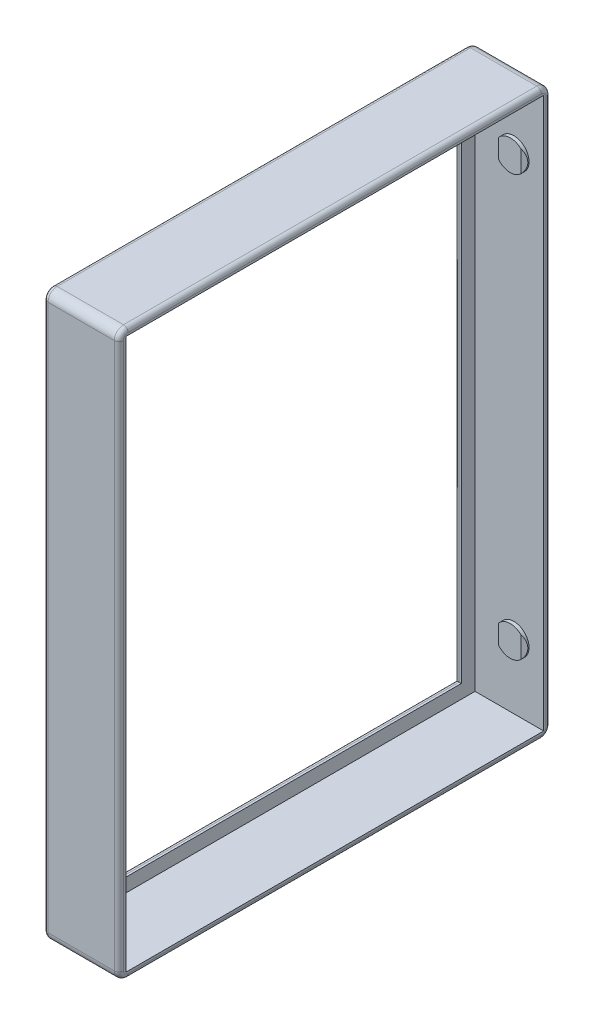
SolidWorks part; units mm, degrees
ref_plane "Front Plane" through (0, 0, 0) normal (0, 0, 1) x (1, 0, 0)
ref_plane "Top Plane" through (0, 0, 0) normal (0, 1, 0) x (1, 0, 0)
ref_plane "Right Plane" through (0, 0, 0) normal (1, 0, 0) x (0, 0, -1)
sketch "Sketch1" plane through (3.3486, 0, 0) normal (-1, 0, 0) x (0, 0, 1)
  line L0 (-28.4017, -129.0389) -> (56.9983, -129.0389)
  line L1 (56.9983, -129.0389) -> (56.9983, -14.6389)
  line L2 (56.9983, -14.6389) -> (-28.4017, -14.6389)
  line L3 (-28.4017, -14.6389) -> (-28.4017, -129.0389)
  line L4 (61.4983, -133.5389) -> (61.4983, -10.1389)
  line L5 (61.4983, -10.1389) -> (-32.9017, -10.1389)
  line L6 (-32.9017, -10.1389) -> (-32.9017, -133.5389)
  line L7 (-32.9017, -133.5389) -> (61.4983, -133.5389)
  line L8 (59.9983, -11.6389) -> (-31.4017, -11.6389)
  line L10 (59.9983, -11.6389) -> (-31.4017, -11.6389)
  line L1256 (-31.4017, -11.6389) -> (-31.4017, -132.0389)
  line L1258 (-31.4017, -11.6389) -> (-31.4017, -132.0389)
  line L1268 (-31.4017, -132.0389) -> (59.9983, -132.0389)
  line L1269 (-31.4017, -132.0389) -> (59.9983, -132.0389)
  line L1270 (59.9983, -132.0389) -> (59.9983, -11.6389)
  line L1271 (59.9983, -132.0389) -> (59.9983, -11.6389)
  dimension "D1" = 0.2
extrude "Boss-Extrude1" add sketch "Sketch1" along normal blind 1.5 contours L6 L7 L4 L5 L1271 L1269 L1258 L10 | L1269 L1271 L10 L1258 L3 L2 L1 L0 region at (3.3486, -133.3835, 14.2983) region at (3.3486, -71.8389, 58.4867)
extrude "Boss-Extrude2" add sketch "Sketch1<3>" against normal blind 15 contours L6 L7 L4 L5 L1271 L1269 L1258 L10 region at (3.3486, -133.3835, 14.2983)
sketch "Sketch1<3>" plane through (3.3486, 0, 0) normal (-1, 0, 0) x (0, 0, 1) same geometry as "Sketch1"
fillet "Fillet1" radius 2 4 edges at (10.0986, -10.1389, -32.9017) (10.0986, -133.5389, -32.9017) (10.0986, -10.1389, 61.4983) (10.0986, -133.5389, 61.4983)
fillet "Fillet2" radius 1 12 edges at (1.8486, -129.0389, 14.2983) (1.8486, -71.8389, 56.9983) (1.8486, -14.6389, 14.2983) (1.8486, -71.8389, -28.4017) (1.8486, -10.7247, 60.9125) (1.8486, -71.8389, 61.4983) (1.8486, -132.9531, 60.9125) (1.8486, -133.5389, 14.2983) (1.8486, -132.9531, -32.3159) (1.8486, -71.8389, -32.9017) (1.8486, -10.7247, -32.3159) (1.8486, -10.1389, 14.2983)
fillet "Fillet5" radius 1 8 edges at (18.3486, -10.7247, -32.3159) (18.3486, -10.1389, 14.2983) (18.3486, -10.7247, 60.9125) (18.3486, -71.8389, 61.4983) (18.3486, -132.9531, 60.9125) (18.3486, -133.5389, 14.2983) (18.3486, -132.9531, -32.3159) (18.3486, -71.8389, -32.9017)
sketch "Sketch3" plane through (0, 0, 59.9983) normal (0, 0, -1) x (-1, 0, 0)
  line L0 (-9.2237, -23.8389) -> (-9.2237, -27.8389)
  line L1 (-9.2237, -115.8389) -> (-9.2237, -119.8389)
  circle A0 centre (-11.8486, -117.8389) radius 3.5 construction
  circle A1 centre (-11.8486, -25.8389) radius 3.5 construction
  circle A2 centre (-11.8486, -117.8389) radius 3.5 construction
  circle A3 centre (-11.8486, -25.8389) radius 3.5 construction
  circle A4 centre (-11.8486, -25.8389) radius 3.3
  circle A5 centre (-11.8486, -117.8389) radius 3.3
  dimension "D2" = 4
  dimension "D3" = 4
  dimension "D1" = 0.2
extrude "Boss-Extrude3" add sketch "Sketch3" along normal blind 0.8 contours L1 A5 | L0 A4 region at (12.0134, -25.8389, 59.9983) region at (12.0134, -117.8389, 59.9983)
extrude "Boss-Extrude4" add sketch "Sketch3<3>" against normal blind 0.8 from surface contours L1 A5 | L0 A4 region at (12.0134, -25.8389, 59.9983) region at (12.0134, -117.8389, 59.9983) starting at face at (10.8486, -71.8389, -31.4017)
sketch "Sketch3<3>" plane through (0, 0, 59.9983) normal (0, 0, -1) x (-1, 0, 0) same geometry as "Sketch3"
sketch "Sketch5" plane through (0, -132.0389, 0) normal (0, 1, 0) x (1, 0, 0)
  line L0 (15.6486, 31.4017) -> (14.1486, 30.6017)
  line L1 (18.3486, 31.4017) -> (3.3486, 31.4017) construction
  line L2 (15.1486, 30.6017) -> (9.2237, 30.6017) construction
  line L3 (15.1486, 30.6017) -> (9.2237, 30.6017) construction
  line L4 (14.1486, 30.6017) -> (15.6486, 30.6017)
  line L5 (15.6486, 30.6017) -> (15.6486, 31.4017)
  line L6 (15.1486, -59.1983) -> (9.2237, -59.1983) construction
  line L7 (15.1486, -59.1983) -> (9.2237, -59.1983) construction
  line L8 (15.6486, -59.9983) -> (14.1486, -59.1983)
  line L9 (18.3486, -59.9983) -> (3.3486, -59.9983) construction
  line L10 (14.1486, -59.1983) -> (15.6486, -59.1983)
  line L11 (15.6486, -59.1983) -> (15.6486, -59.9983)
  dimension "D1" = 0.5
  dimension "D2" = 1
  dimension "D3" = 0.5
  dimension "D4" = 1
extrude "Cut-Extrude1" cut sketch "Sketch5" along normal up to surface (120.4 mm away) up to face at (10.8486, -11.6389, 14.2983)
